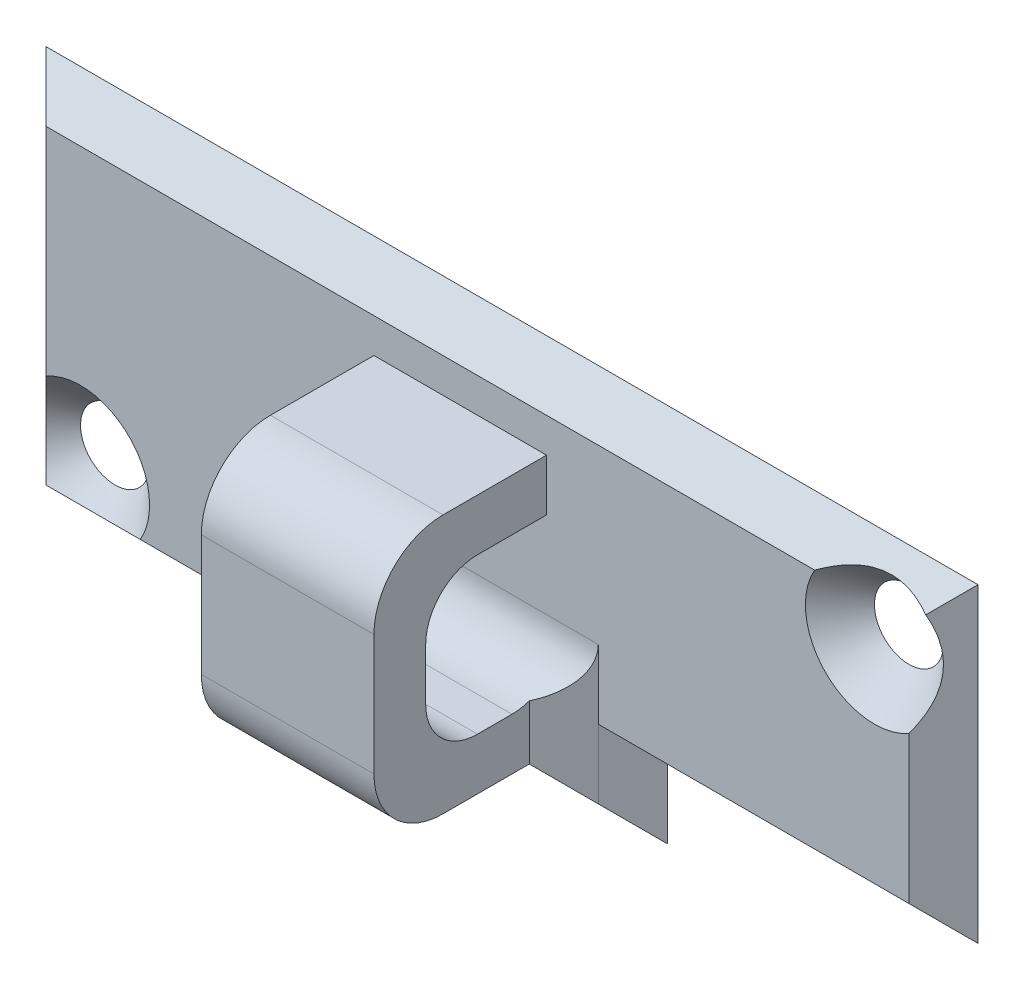
SolidWorks part; units mm, degrees
ref_plane "Front Plane" through (0, 0, 0) normal (0, 0, 1) x (1, 0, 0)
ref_plane "Top Plane" through (0, 0, 0) normal (0, 1, 0) x (1, 0, 0)
ref_plane "Right Plane" through (0, 0, 0) normal (1, 0, 0) x (0, 0, -1)
sketch "Sketch1" plane through (0, 0, 0) normal (0, 0, 1) x (1, 0, 0)
  line L1 (-13.5, -5.5) -> (13.5, -5.5)
  line L2 (-13.5, -5.5) -> (-13.5, 5.5)
  line L3 (-13.5, 5.5) -> (13.5, 5.5)
  line L4 (13.5, -5.5) -> (13.5, 5.5)
  line L5 (-13.5, -5.5) -> (13.5, 5.5) construction
  line L6 (-13.5, 5.5) -> (13.5, -5.5) construction
  line L7 (4.5, -3.5) -> (13.5, -3.5)
  line L8 (4.5, -3.5) -> (4.5, -7.5)
  line L9 (4.5, -7.5) -> (13.5, -7.5)
  line L10 (13.5, -3.5) -> (13.5, -7.5)
  line L11 (4.5, -3.5) -> (13.5, -7.5) construction
  line L12 (4.5, -7.5) -> (13.5, -3.5) construction
  circle A0 centre (-11.5, -3.5) radius 1
  circle A1 centre (11.5, 3.5) radius 1
  point P0 (0, 0)
  point P6 (9, -5.5)
  dimension "D3" = 2
  dimension "D4" = 2
  dimension "D5" = 2
  dimension "D6" = 2
  dimension "D7" = 2
  dimension "D1" = 11
  dimension "D2" = 27
  dimension "D8" = 9
  dimension "D10" = 2
extrude "Boss-Extrude1" add sketch "Sketch1" along normal blind 1 contours L7 L10 L1 L4 L3 L2 L8 A1 A0 region at (-0.594, 0.297, 0)
sketch "Sketch3" plane through (0, 0, 0) normal (1, 0, 0) x (0, 0, -1)
  line L0 (-1, -3.5) -> (-6.5, -3.5)
  line L1 (-1, -3.5) -> (-1, 5.5) construction
  line L2 (-6.5, -3.5) -> (-6.5, 4)
  line L6 (-1, -2) -> (-1, -3.5)
  line L7 (-1, -2) -> (-5, -2)
  line L8 (-5, -2) -> (-5, 2.5)
  line L9 (-5, 2.5) -> (-1.5, 2.5)
  line L10 (-1.5, 2.5) -> (-1.5, 4)
  line L11 (-1.5, 4) -> (-6.5, 4)
  line L12 (-1, -5.5) -> (0, -5.5) construction
  dimension "D1" = 1.5
  dimension "D2" = 1.5
  dimension "D3" = 0.5
  dimension "D4" = 4
  dimension "D5" = 4.5
  dimension "D6" = 2
extrude "Boss-Extrude6" add sketch "Sketch3" against normal mid plane 5
fillet "Fillet6" radius 1.5 3 edges at (0, 2.5, 5) (0, -2, 5) (0, -2, 1)
fillet "Fillet7" radius 2 2 edges at (0, 4, 6.5) (0, -3.5, 6.5)
chamfer "Chamfer1" distance 1 angle 45 11 edges at (-4.5, -5.5, 1) (-13.5, 0, 1) (0, 5.5, 1) (13.5, 1, 1) (9, -3.5, 1) (4.5, -4.5, 1) (-10.5, -3.5, 1) (12.5, 3.5, 1) (-2.5, -2, 1) (0, -3.5, 1) (2.5, -2, 1)
